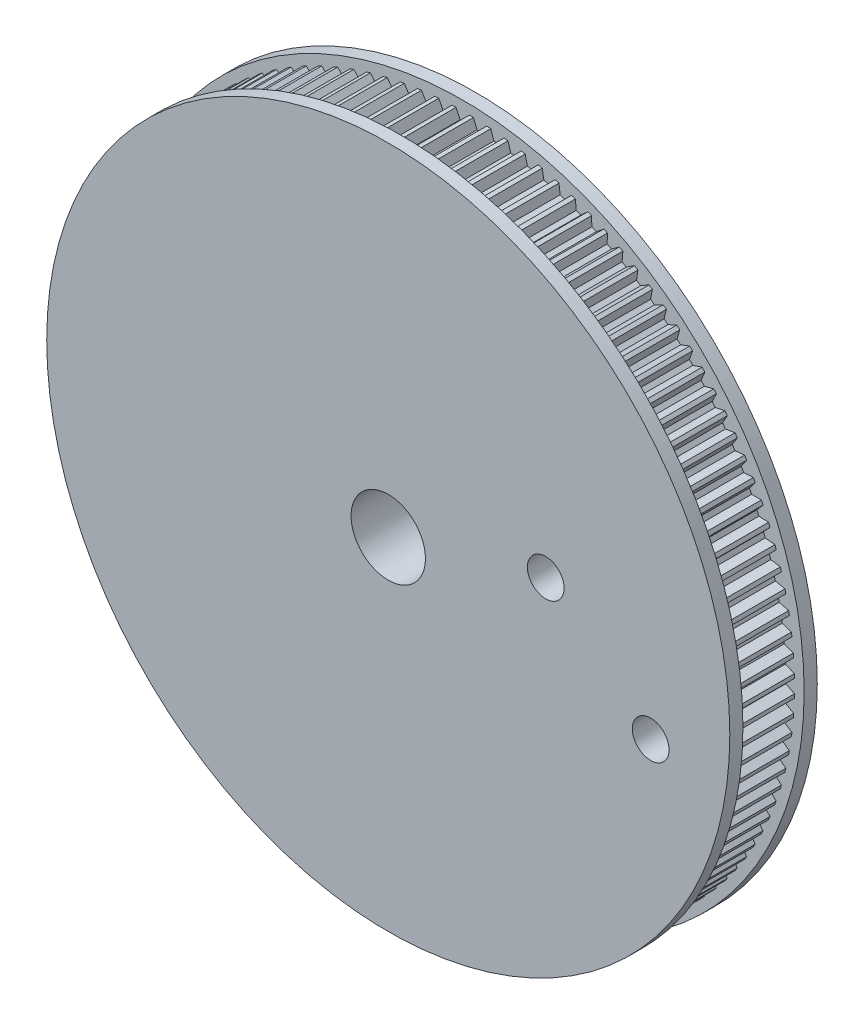
SolidWorks part; units mm, degrees
note: The reader was unsure of these and kept them because the rebuilt part matched: shared geometry of "Sketch6<3>".
ref_plane "Front Plane" through (0, 0, 0) normal (0, 0, 1) x (1, 0, 0)
ref_plane "Top Plane" through (0, 0, 0) normal (0, 1, 0) x (1, 0, 0)
ref_plane "Right Plane" through (0, 0, 0) normal (1, 0, 0) x (0, 0, -1)
sketch "Sketch1" plane through (0, 0, 0) normal (0, 0, 1) x (1, 0, 0)
  line L0 (0, 0) -> (0, 70.3884) construction
  line L7 (-45.5558, 37.945) -> (35.6533, 37.945) construction
  line L176 (0, 11.1) -> (36.2852, 11.1) construction
  line L177 (0, -11.1) -> (36.2852, -11.1) construction
  line L178 (0, 0) -> (61.345, 0) construction
  circle A0 centre (0, 0) radius 37.945
  circle A1 centre (0, 0) radius 4.25
  circle A3 centre (0, 0) radius 11.1
  circle A5 centre (18, 5) radius 2.1
  circle A7 centre (30, -5) radius 2.1
  circle A9 centre (30, 5) radius 2.1 [skipped]
  circle A10 centre (18, -5) radius 2.1 [skipped]
  point P123 (0, 0)
  point P176 (0, 0)
  point P190 (0, 0)
  dimension "D1" = 75.89
  dimension "8mm" = 8.5
  dimension "R_608z" = 22.2
  dimension "D9" = 2
  dimension "4mm" = 4.2
  dimension "D7" = 18
  dimension "D8" = 5
  dimension "D10" = 2
extrude "Boss-Extrude1" add sketch "Sketch1" along normal blind 10
sketch "Sketch3" plane through (0, 0, 10) normal (0, 0, 1) x (1, 0, 0)
  line L0 (0, 0) -> (0, 54.3993) construction
  line L1 (-70.5656, 37.945) -> (-54.4781, 37.945) construction
  line L2 (-0.28, 36.945) -> (0.28, 36.945)
  line L3 (0.28, 36.945) -> (0.78, 37.937)
  line L5 (-0.75, 37.9376) -> (-0.28, 36.945)
  circle A0 centre (0, 0) radius 37.945 construction
  arc A1 (0.78, 37.937) -> (-0.75, 37.9376) centre (0, 0) ccw
  point P11 (0, 36.945)
  dimension "D1" = 1
  dimension "D2" = 0.56
  dimension "D3" = 0.78
  dimension "D4" = 0.75
extrude "Cut-Extrude2" cut sketch "Sketch3" against normal blind 10
pattern_circular "CirPattern2" count 120 over 360 about axis through (0, 0, 0) along (0, 0, 1) of "Cut-Extrude2"
sketch "Sketch6" plane through (0, 0, 10) normal (0, 0, 1) x (1, 0, 0)
  circle A0 centre (0, 0) radius 37.945 construction
  circle A1 centre (0, 0) radius 37.945 construction
  circle A2 centre (0, 0) radius 39.045
  circle A3 centre (0, 0) radius 35.945
  dimension "D1" = 1.1
  dimension "D2" = 2
extrude "Boss-Extrude4" add sketch "Sketch6" along normal blind 1.5 from surface at -10 starting at face at (0, 0, 0)
extrude "Boss-Extrude5" add sketch "Sketch6<3>" against normal blind 1.5 from surface at 0 starting at face at (0, 0, 10)
sketch "Sketch6<3>" plane through (0, 0, 10) normal (0, 0, 1) x (1, 0, 0) same geometry as "Sketch6"
